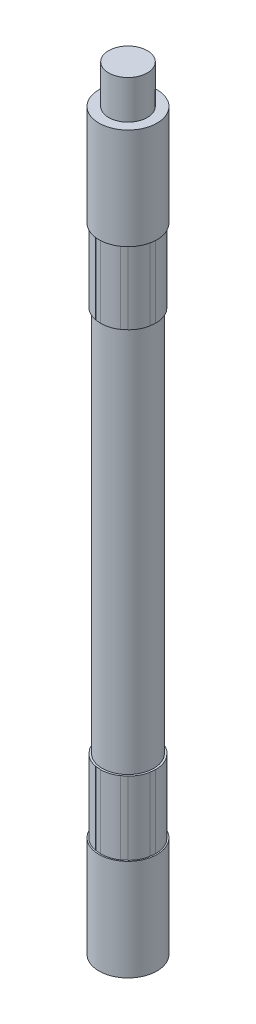
SolidWorks part; units mm, degrees
ref_plane "Front Plane" through (0, 0, 0) normal (0, 0, 1) x (1, 0, 0)
ref_plane "Top Plane" through (0, 0, 0) normal (0, 1, 0) x (1, 0, 0)
ref_plane "Right Plane" through (0, 0, 0) normal (1, 0, 0) x (0, 0, -1)
sketch "Sketch1" plane through (0, 0, 0) normal (0, 1, 0) x (1, 0, 0)
  circle A0 centre (0, 0) radius 14.2875
  dimension "D1" = 28.575
extrude "Boss-Extrude1" add sketch "Sketch1" along normal blind 180.975 and the other way blind 180.975
sketch "Sketch2" plane through (0, 0, 0) normal (0, 1, 0) x (1, 0, 0)
  circle A0 centre (0, 0) radius 12.7
  dimension "D1" = 25.4
extrude "Cut-Extrude1" cut sketch "Sketch2" against normal blind 95.25 and the other way blind 95.25 flip side to cut
sketch "Sketch3" plane through (0, 0, 0) normal (0, 1, 0) x (1, 0, 0)
  circle A0 centre (0, 0) radius 13.6525
  dimension "D1" = 27.305
extrude "Cut-Extrude2" cut sketch "Sketch3" against normal blind 131.191 and the other way blind 131.191 flip side to cut
sketch "Sketch5" plane through (0, -131.191, 0) normal (0, 1, 0) x (1, 0, 0)
  line L0 (0, -13.6525) -> (0, -13.5509)
  line L1 (-2.5418, -13.4138) -> (-2.5229, -13.314)
  line L2 (-9.6538, -9.6538) -> (-9.5819, -9.5819)
  line L3 (-11.2823, -7.6876) -> (-11.1984, -7.6304)
  line L4 (-13.6525, 0) -> (-13.5509, 0)
  line L5 (-13.4138, 2.5418) -> (-13.314, 2.5229)
  line L6 (-9.6538, 9.6538) -> (-9.5819, 9.5819)
  line L7 (-7.6876, 11.2823) -> (-7.6304, 11.1984)
  line L8 (0, 13.6525) -> (0, 13.5509)
  line L9 (2.5418, 13.4138) -> (2.5229, 13.314)
  line L10 (9.6538, 9.6538) -> (9.5819, 9.5819)
  line L11 (11.2823, 7.6876) -> (11.1984, 7.6304)
  line L12 (13.6525, 0) -> (13.5509, 0)
  line L13 (13.4138, -2.5418) -> (13.314, -2.5229)
  line L14 (9.6538, -9.6538) -> (9.5819, -9.5819)
  line L15 (7.6876, -11.2823) -> (7.6304, -11.1984)
  arc A0 (0, -13.6525) -> (7.6876, -11.2823) centre (0, 0) ccw
  arc A1 (9.6538, -9.6538) -> (13.4138, -2.5418) centre (0, 0) ccw
  arc A2 (-2.5229, -13.314) -> (0, -13.5509) centre (0, 0) ccw
  circle A3 centre (0, 0) radius 13.6525 construction
  circle A4 centre (0, 0) radius 13.5509
  arc A5 (7.6304, -11.1984) -> (9.5819, -9.5819) centre (0, 0) ccw
  circle A6 centre (0, 0) radius 13.6525 construction
  arc A7 (-9.6538, -9.6538) -> (-2.5418, -13.4138) centre (0, 0) ccw
  arc A8 (-11.1984, -7.6304) -> (-9.5819, -9.5819) centre (0, 0) ccw
  arc A9 (-13.6525, 0) -> (-11.2823, -7.6876) centre (0, 0) ccw
  arc A10 (-13.314, 2.5229) -> (-13.5509, 0) centre (0, 0) ccw
  arc A11 (-9.6538, 9.6538) -> (-13.4138, 2.5418) centre (0, 0) ccw
  arc A12 (-7.6304, 11.1984) -> (-9.5819, 9.5819) centre (0, 0) ccw
  arc A13 (0, 13.6525) -> (-7.6876, 11.2823) centre (0, 0) ccw
  arc A14 (2.5229, 13.314) -> (0, 13.5509) centre (0, 0) ccw
  arc A15 (9.6538, 9.6538) -> (2.5418, 13.4138) centre (0, 0) ccw
  arc A16 (11.1984, 7.6304) -> (9.5819, 9.5819) centre (0, 0) ccw
  arc A17 (13.6525, 0) -> (11.2823, 7.6876) centre (0, 0) ccw
  arc A18 (13.314, -2.5229) -> (13.5509, 0) centre (0, 0) ccw
  point P10 (0, 0)
  point P42 (0, 0)
  dimension "D2" = 2
  dimension "D3" = 8
  dimension "D1" = 0.1016
sketch "Sketch6" plane through (0, 131.191, 0) normal (0, -1, 0) x (1, 0, 0)
  line L0 (-13.6525, 0) -> (-13.5509, 0) construction
  line L1 (-13.4138, -2.5418) -> (-13.314, -2.5229) construction
  line L2 (-9.6538, -9.6538) -> (-9.5819, -9.5819) construction
  line L3 (-7.6876, -11.2823) -> (-7.6304, -11.1984) construction
  line L4 (0, -13.6525) -> (0, -13.5509) construction
  line L5 (2.5418, -13.4138) -> (2.5229, -13.314) construction
  line L6 (9.6538, -9.6538) -> (9.5819, -9.5819) construction
  line L7 (11.2823, -7.6876) -> (11.1984, -7.6304) construction
  line L8 (13.6525, 0) -> (13.5509, 0) construction
  line L9 (13.4138, 2.5418) -> (13.314, 2.5229) construction
  line L10 (9.6538, 9.6538) -> (9.5819, 9.5819) construction
  line L11 (7.6876, 11.2823) -> (7.6304, 11.1984) construction
  line L12 (0, 13.6525) -> (0, 13.5509) construction
  line L13 (-2.5418, 13.4138) -> (-2.5229, 13.314) construction
  line L14 (-9.6538, 9.6538) -> (-9.5819, 9.5819) construction
  line L15 (-11.2823, 7.6876) -> (-11.1984, 7.6304) construction
  line L16 (-13.6525, 0) -> (-13.5509, 0)
  line L17 (-13.4138, -2.5418) -> (-13.314, -2.5229)
  line L18 (-9.6538, -9.6538) -> (-9.5819, -9.5819)
  line L19 (-7.6876, -11.2823) -> (-7.6304, -11.1984)
  line L20 (0, -13.6525) -> (0, -13.5509)
  line L21 (2.5418, -13.4138) -> (2.5229, -13.314)
  line L22 (9.6538, -9.6538) -> (9.5819, -9.5819)
  line L23 (11.2823, -7.6876) -> (11.1984, -7.6304)
  line L24 (13.6525, 0) -> (13.5509, 0)
  line L25 (13.4138, 2.5418) -> (13.314, 2.5229)
  line L26 (9.6538, 9.6538) -> (9.5819, 9.5819)
  line L27 (7.6876, 11.2823) -> (7.6304, 11.1984)
  line L28 (0, 13.6525) -> (0, 13.5509)
  line L29 (-2.5418, 13.4138) -> (-2.5229, 13.314)
  line L30 (-9.6538, 9.6538) -> (-9.5819, 9.5819)
  line L31 (-11.2823, 7.6876) -> (-11.1984, 7.6304)
  arc A0 (-13.5509, 0) -> (-13.314, -2.5229) centre (0, 0) ccw construction
  circle A1 centre (0, 0) radius 14.2875
  circle A2 centre (0, 0) radius 14.2875
  arc A3 (-13.4138, -2.5418) -> (-9.6538, -9.6538) centre (0, 0) ccw construction
  arc A4 (-9.5819, -9.5819) -> (-7.6304, -11.1984) centre (0, 0) ccw construction
  arc A5 (-7.6876, -11.2823) -> (0, -13.6525) centre (0, 0) ccw construction
  arc A6 (0, -13.5509) -> (2.5229, -13.314) centre (0, 0) ccw construction
  arc A7 (2.5418, -13.4138) -> (9.6538, -9.6538) centre (0, 0) ccw construction
  arc A8 (9.5819, -9.5819) -> (11.1984, -7.6304) centre (0, 0) ccw construction
  arc A9 (11.2823, -7.6876) -> (13.6525, 0) centre (0, 0) ccw construction
  arc A10 (13.5509, 0) -> (13.314, 2.5229) centre (0, 0) ccw construction
  arc A11 (13.4138, 2.5418) -> (9.6538, 9.6538) centre (0, 0) ccw construction
  arc A12 (9.5819, 9.5819) -> (7.6304, 11.1984) centre (0, 0) ccw construction
  arc A13 (7.6876, 11.2823) -> (0, 13.6525) centre (0, 0) ccw construction
  arc A14 (0, 13.5509) -> (-2.5229, 13.314) centre (0, 0) ccw construction
  arc A15 (-2.5418, 13.4138) -> (-9.6538, 9.6538) centre (0, 0) ccw construction
  arc A16 (-9.5819, 9.5819) -> (-11.1984, 7.6304) centre (0, 0) ccw construction
  arc A17 (-11.2823, 7.6876) -> (-13.6525, 0) centre (0, 0) ccw construction
  arc A18 (-13.5509, 0) -> (-13.314, -2.5229) centre (0, 0) ccw
  arc A19 (-13.4138, -2.5418) -> (-9.6538, -9.6538) centre (0, 0) ccw
  arc A20 (-9.5819, -9.5819) -> (-7.6304, -11.1984) centre (0, 0) ccw
  arc A21 (-7.6876, -11.2823) -> (0, -13.6525) centre (0, 0) ccw
  arc A22 (0, -13.5509) -> (2.5229, -13.314) centre (0, 0) ccw
  arc A23 (2.5418, -13.4138) -> (9.6538, -9.6538) centre (0, 0) ccw
  arc A24 (9.5819, -9.5819) -> (11.1984, -7.6304) centre (0, 0) ccw
  arc A25 (11.2823, -7.6876) -> (13.6525, 0) centre (0, 0) ccw
  arc A26 (13.5509, 0) -> (13.314, 2.5229) centre (0, 0) ccw
  arc A27 (13.4138, 2.5418) -> (9.6538, 9.6538) centre (0, 0) ccw
  arc A28 (9.5819, 9.5819) -> (7.6304, 11.1984) centre (0, 0) ccw
  arc A29 (7.6876, 11.2823) -> (0, 13.6525) centre (0, 0) ccw
  arc A30 (0, 13.5509) -> (-2.5229, 13.314) centre (0, 0) ccw
  arc A31 (-2.5418, 13.4138) -> (-9.6538, 9.6538) centre (0, 0) ccw
  arc A32 (-9.5819, 9.5819) -> (-11.1984, 7.6304) centre (0, 0) ccw
  arc A33 (-11.2823, 7.6876) -> (-13.6525, 0) centre (0, 0) ccw
  dimension "D1" = 0
extrude "Cut-Extrude4" cut sketch "Sketch5" along normal up to surface (35.941 mm away) flip side to cut up to face at (0, -95.25, 12.7)
extrude "Cut-Extrude7" cut sketch "Sketch6" along normal up to surface (35.941 mm away) up to face at (0, 95.25, 12.7)
sketch "Sketch7" plane through (0, 180.975, 0) normal (0, 1, 0) x (1, 0, 0)
  circle A0 centre (0, 0) radius 9.525
  dimension "D1" = 19.05
extrude "Boss-Extrude2" add sketch "Sketch7" along normal blind 19.05
